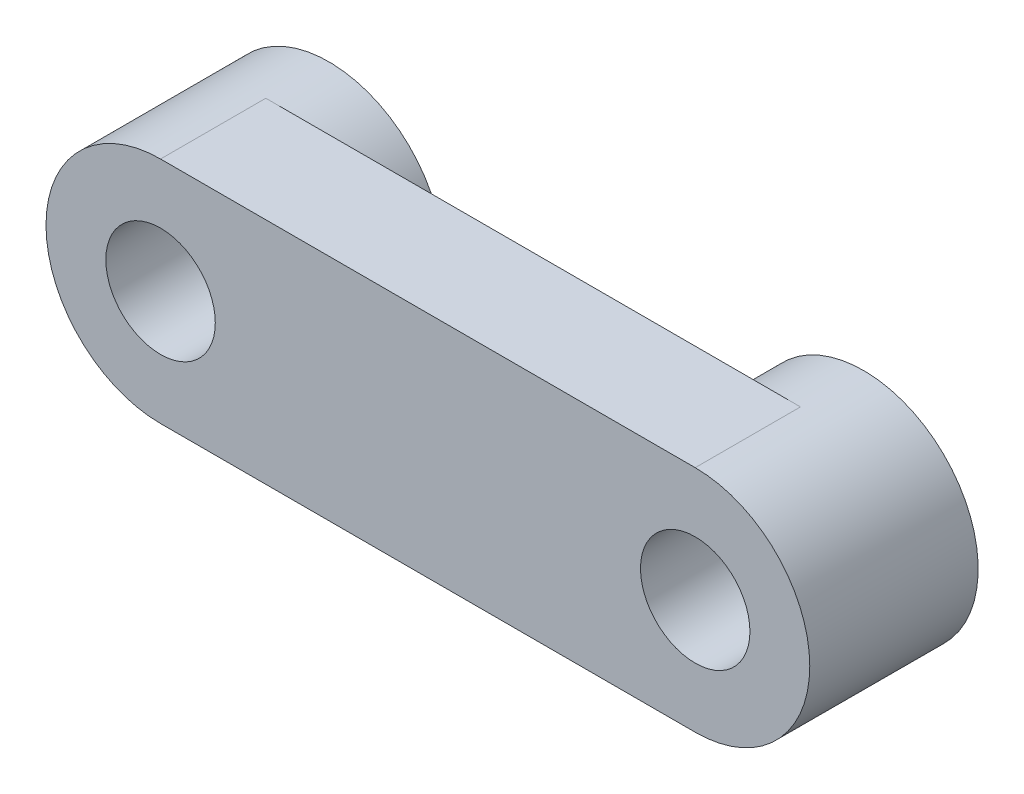
SolidWorks part; units mm, degrees
ref_plane "Front Plane" through (0, 0, 0) normal (0, 0, 1) x (1, 0, 0)
ref_plane "Top Plane" through (0, 0, 0) normal (0, 1, 0) x (1, 0, 0)
ref_plane "Right Plane" through (0, 0, 0) normal (1, 0, 0) x (0, 0, -1)
sketch "Sketch1" plane through (0, 0, 0) normal (0, 0, 1) x (1, 0, 0)
  line L0 (-12.7, 0) -> (12.7, 0) construction
  line L1 (-12.7, 5.4429) -> (12.7, 5.4429)
  line L2 (-12.7, -5.4429) -> (12.7, -5.4429)
  arc A0 (-12.7, 5.4429) -> (-12.7, -5.4429) centre (-12.7, 0) ccw
  arc A1 (12.7, -5.4429) -> (12.7, 5.4429) centre (12.7, 0) ccw
  circle A2 centre (-12.7, 0) radius 2.6
  circle A3 centre (12.7, 0) radius 2.6
  point P2 (0, 0)
  dimension "D2" = 5.2
  dimension "D1" = 25.4
extrude "Boss-Extrude1" add sketch "Sketch1" along normal blind 5
sketch "Sketch2" plane through (0, 0, 0) normal (0, 0, -1) x (-1, 0, 0)
  circle A0 centre (-12.7, 0) radius 5.4429
  arc A1 (-12.7, 5.4429) -> (-12.7, -5.4429) centre (-12.7, 0) ccw construction
  circle A2 centre (12.7, 0) radius 5.4429
  arc A3 (12.7, -5.4429) -> (12.7, 5.4429) centre (12.7, 0) ccw construction
  circle A4 centre (12.7, 0) radius 2.6 construction
  circle A5 centre (-12.7, 0) radius 2.6 construction
  circle A6 centre (12.7, 0) radius 2.6
  circle A7 centre (-12.7, 0) radius 2.6
extrude "Boss-Extrude2" add sketch "Sketch2" along normal blind 3
